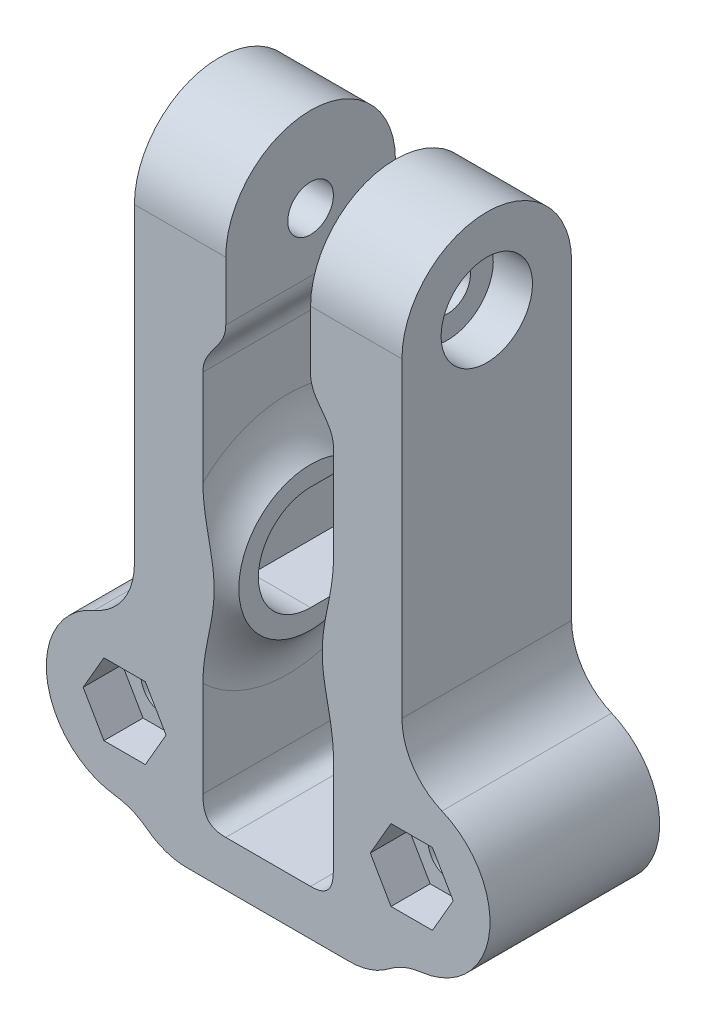
SolidWorks part; units mm, degrees
ref_plane "Front Plane" through (0, 0, 0) normal (0, 0, 1) x (1, 0, 0)
ref_plane "Top Plane" through (0, 0, 0) normal (0, 1, 0) x (1, 0, 0)
ref_plane "Right Plane" through (0, 0, 0) normal (1, 0, 0) x (0, 0, -1)
sketch "Sketch1" plane through (0, 0, 0) normal (0, 0, 1) x (1, 0, 0)
  line L0 (-3.25, 0) -> (-3.25, -45)
  line L1 (-3.25, -45) -> (3.25, -45)
  line L2 (3.25, -45) -> (3.25, 0)
  line L3 (3.25, 0) -> (10.25, 0)
  line L4 (10.25, 0) -> (10.25, -48.5)
  line L5 (10.25, -48.5) -> (-10.25, -48.5)
  line L6 (-10.25, -48.5) -> (-10.25, 0)
  line L7 (-10.25, 0) -> (-3.25, 0)
  dimension "D1" = 6.5
  dimension "D2" = 3.25
  dimension "D3" = 45
  dimension "D4" = 7
  dimension "D5" = 3.5
extrude "Boss-Extrude1" add sketch "Sketch1" along normal blind 13
sketch "Sketch2" plane through (10.25, 0, 0) normal (1, 0, 0) x (0, 0, -1)
  line L0 (-6.5, 0) -> (-6.5, -48.5) construction
  line L1 (-13, 0) -> (0, 0) construction
  line L2 (-13, -48.5) -> (0, -48.5) construction
  line L3 (-13, -6.5) -> (-21.1298, -6.5)
  line L4 (-21.1298, -6.5) -> (-21.1298, 2.8811)
  line L5 (-21.1298, 2.8811) -> (14.28, 2.8811)
  line L6 (14.28, 2.8811) -> (14.28, -6.5)
  line L7 (14.28, -6.5) -> (0, -6.5)
  circle A0 centre (-6.5, -6.5) radius 1.75
  arc A1 (0, -6.5) -> (-13, -6.5) centre (-6.5, -6.5) ccw
  dimension "D1" = 3.5
  dimension "D2" = 13
extrude "Cut-Extrude1" cut sketch "Sketch2" against normal up to surface (20.5 mm away) up to face at (-10.25, -24.25, 6.5)
sketch "Sketch4" plane through (0, 0, 13) normal (0, 0, 1) x (1, 0, 0)
  line L0 (3.25, -45) -> (-3.25, -45) construction
  line L1 (-5, -15) -> (5, -15)
  line L2 (-5, -15) -> (-5, -43)
  line L3 (-5, -43) -> (5, -43)
  line L4 (5, -15) -> (5, -43)
  dimension "D1" = 10
  dimension "D2" = 5
  dimension "D3" = 28
  dimension "D4" = 2
extrude "Cut-Extrude2" cut sketch "Sketch4" against normal blind 13
ref_plane "Plane1" through (0, 0, 0) normal (1, 0, 0) x (0, 0, -1)
sketch "Sketch7" plane through (0, 0, 0) normal (1, 0, 0) x (0, 0, -1)
  line L0 (-6.5, -15) -> (-6.5, -43) construction
  line L1 (0, -15) -> (-13, -15) construction
  line L2 (0, -43) -> (-13, -43) construction
  line L3 (-6.5, -25) -> (0, -25)
  line L4 (0, -48.5) -> (0, -6.5) construction
  line L5 (0, -25) -> (0, -33)
  line L6 (0, -33) -> (-6.5, -33)
  arc A0 (-6.5, -25) -> (-6.5, -33) centre (-6.5, -29) ccw
  circle A1 centre (-6.5, -29) radius 11 construction
  dimension "D1" = 8
  dimension "D2" = 22
extrude "Cut-Extrude3" cut sketch "Sketch7" against normal offset from surface 2.5 and the other way offset from surface 2.5 up to face at (-10.25, -4.75, 6.5) other way up to face at (10.25, -4.75, 6.5)
sketch "Sketch8" plane through (0, 0, 0) normal (0, 0, -1) x (-1, 0, 0)
  line L0 (11, -40.5) -> (-11, -40.5) construction
  line L1 (0, 7.15) -> (0, -7.15) construction
  line L2 (10.25, -48.5) -> (-10.25, -48.5) construction
  circle A0 centre (11, -40.5) radius 6
  circle A1 centre (-11, -40.5) radius 6
  dimension "D1" = 22
  dimension "D3" = 12
  dimension "D2" = 11
  dimension "D4" = 8
extrude "Boss-Extrude2" add sketch "Sketch8" against normal up to surface (13 mm away) up to face at (0, -27.8125, 13)
sketch "Sketch9" plane through (0, 0, 0) normal (0, 0, -1) x (-1, 0, 0)
  circle A0 centre (11, -40.5) radius 1.75
  circle A1 centre (-11, -40.5) radius 1.75
  dimension "D1" = 3.5
extrude "Cut-Extrude4" cut sketch "Sketch9" against normal up to next
sketch "Sketch10" plane through (0, 0, 0) normal (0, 0, -1) x (-1, 0, 0)
  circle A0 centre (11, -40.5) radius 4
  circle A1 centre (-11, -40.5) radius 4
  dimension "D1" = 8
extrude "Cut-Extrude5" cut sketch "Sketch10" against normal blind 3
sketch "Sketch11" plane through (0, 0, 13) normal (0, 0, 1) x (1, 0, 0)
  line L1 (14.1754, -40.5) -> (12.5877, -37.75)
  line L2 (12.5877, -37.75) -> (9.4123, -37.75)
  line L3 (9.4123, -37.75) -> (7.8246, -40.5)
  line L4 (7.8246, -40.5) -> (9.4123, -43.25)
  line L5 (9.4123, -43.25) -> (12.5877, -43.25)
  line L6 (12.5877, -43.25) -> (14.1754, -40.5)
  line L7 (-7.8246, -40.5) -> (-9.4123, -37.75)
  line L8 (-9.4123, -37.75) -> (-12.5877, -37.75)
  line L9 (-12.5877, -37.75) -> (-14.1754, -40.5)
  line L10 (-14.1754, -40.5) -> (-12.5877, -43.25)
  line L11 (-12.5877, -43.25) -> (-9.4123, -43.25)
  line L12 (-9.4123, -43.25) -> (-7.8246, -40.5)
  circle A0 centre (11, -40.5) radius 2.75 construction
  circle A1 centre (-11, -40.5) radius 2.75 construction
  dimension "D1" = 5.5
extrude "Cut-Extrude6" cut sketch "Sketch11" against normal blind 3
sketch "Sketch12" plane through (-5, 0, 0) normal (1, 0, 0) x (0, 0, -1)
  line L0 (-6.5, -25) -> (0, -25) construction
  line L1 (0, -33) -> (-6.5, -33) construction
  line L2 (-6.5, -25) -> (-2.7251, -25)
  line L3 (-2.7251, -33) -> (-6.5, -33)
  arc A0 (-2.7251, -25) -> (-2.7251, -33) centre (-6.5, -29) ccw
  arc A1 (-6.5, -25) -> (-6.5, -33) centre (-6.5, -29) ccw construction
  arc A2 (-6.5, -25) -> (-6.5, -33) centre (-6.5, -29) ccw
  dimension "D1" = 11
extrude "Boss-Extrude3" add sketch "Sketch12" along normal blind 1.75
fillet "Fillet1" radius 5 1 edges at (-5, -29, 12)
sketch "Sketch13" plane through (5, 0, 0) normal (-1, 0, 0) x (0, 0, 1)
  line L0 (6.5, -25) -> (0, -25) construction
  line L1 (0, -33) -> (6.5, -33) construction
  line L2 (6.5, -25) -> (2.7251, -25)
  line L3 (2.7251, -33) -> (6.5, -33)
  arc A0 (6.5, -33) -> (6.5, -25) centre (6.5, -29) ccw construction
  arc A1 (2.7251, -33) -> (2.7251, -25) centre (6.5, -29) ccw construction
  arc A2 (6.5, -33) -> (6.5, -25) centre (6.5, -29) ccw
  arc A3 (2.7251, -33) -> (2.7251, -25) centre (6.5, -29) ccw
extrude "Boss-Extrude4" add sketch "Sketch13" along normal blind 1.75
fillet "Fillet2" radius 5 1 edges at (5, -29, 12)
sketch "Sketch14" plane through (10.25, 0, 0) normal (1, 0, 0) x (0, 0, -1)
  circle A0 centre (-6.5, -6.5) radius 3.5
  dimension "D1" = 7
extrude "Cut-Extrude7" cut sketch "Sketch14" against normal blind 3
sketch "Sketch15" plane through (-10.25, 0, 0) normal (-1, 0, 0) x (0, 0, 1)
  line L0 (13, -6.5) -> (13, -34.5471) construction
  line L1 (3.75, -8.0877) -> (6.5, -9.6754)
  line L2 (6.5, -9.6754) -> (9.25, -8.0877)
  line L3 (9.25, -8.0877) -> (9.25, -4.9123)
  line L4 (9.25, -4.9123) -> (6.5, -3.3246)
  line L5 (6.5, -3.3246) -> (3.75, -4.9123)
  line L6 (3.75, -4.9123) -> (3.75, -8.0877)
  circle A0 centre (6.5, -6.5) radius 2.75 construction
  dimension "D1" = 5.5
extrude "Cut-Extrude8" cut sketch "Sketch15" against normal blind 3
fillet "Fillet3" radius 5 4 edges at (10.25, -34.5471, 6.5) (10.25, -48.5, 6.5) (-10.25, -48.5, 6.5) (-10.25, -34.5471, 6.5)
fillet "Fillet4" radius 5 2 edges at (10.25, -46.4529, 6.5) (-10.25, -46.4529, 6.5)
sketch "Sketch16" plane through (0, 0, 0) normal (0, 0, -1) x (-1, 0, 0)
  line L0 (-3.25, -45) -> (3.25, -45) construction
  line L1 (-2.6522, -45) -> (-3.8552, -45) construction
  line L2 (-5, -43) -> (-5, -35.6509) construction
  line L3 (-5, -44.1771) -> (-5, -41.7928) construction
  line L4 (-5, -43) -> (-3.25, -43) construction
  line L5 (-3.25, -43) -> (-3.25, -45) construction
  line L6 (-5, -43) -> (-3.25, -43)
  line L7 (-3.25, -43) -> (-3.25, -45)
  line L8 (0, -45) -> (0, -41.3984) construction
  line L9 (3.25, -43) -> (3.25, -45)
  line L10 (5, -43) -> (3.25, -43)
  spline S0 degree 3 poles (-5, -43) (-5, -44.3333) (-4.5833, -45) (-3.25, -45) knots 0 0 0 0 1 1 1 1
  spline S1 degree 3 poles (5, -43) (5, -44.3333) (4.5833, -45) (3.25, -45) knots 0 0 0 0 1 1 1 1
  dimension "D1" = 4
  dimension "D2" = 4
extrude "Cut-Extrude9" cut sketch "Sketch16" against normal up to next
sketch "Sketch17" plane through (0, 0, 0) normal (0, 0, -1) x (-1, 0, 0)
  line L0 (3.25, -15) -> (3.25, -6.5) construction
  line L1 (5, -15) -> (5, -22.3491) construction
  line L2 (5, -13.7822) -> (5, -16.2207) construction
  line L3 (3.25, -11.7912) -> (3.25, -13.3034) construction
  line L4 (5, -15) -> (3.25, -15) construction
  line L5 (5, -15) -> (3.25, -15)
  line L6 (3.25, -11) -> (3.25, -15)
  line L7 (0, -6.4398) -> (0, -18.4452) construction
  line L8 (0, 7.15) -> (0, -7.15) construction
  line L9 (-3.25, -11) -> (-3.25, -15)
  line L10 (-5, -15) -> (-3.25, -15)
  spline S0 degree 3 poles (5, -15) (5, -13.3333) (3.25, -12.6667) (3.25, -11) knots 0 0 0 0 1 1 1 1
  spline S1 degree 3 poles (-5, -15) (-5, -13.3333) (-3.25, -12.6667) (-3.25, -11) knots 0 0 0 0 1 1 1 1
  dimension "D1" = 5
  dimension "D2" = 5
  dimension "D3" = 4
extrude "Cut-Extrude10" cut sketch "Sketch17" against normal up to next
